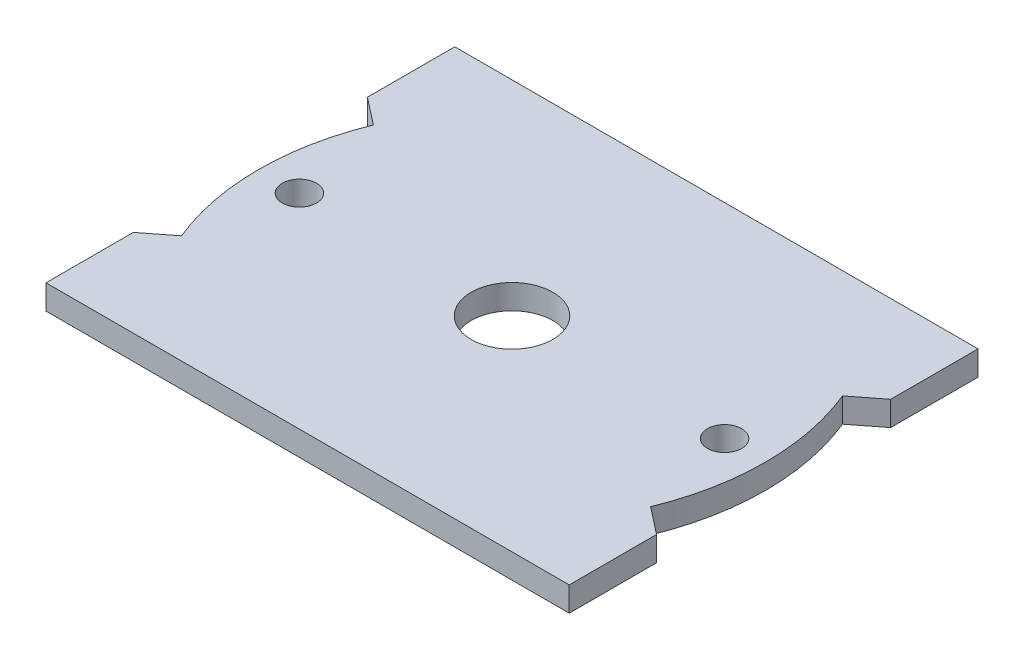
SolidWorks part; units mm, degrees
ref_plane "Front Plane" through (0, 0, 0) normal (0, 0, 1) x (1, 0, 0)
ref_plane "Top Plane" through (0, 0, 0) normal (0, 1, 0) x (1, 0, 0)
ref_plane "Right Plane" through (0, 0, 0) normal (1, 0, 0) x (0, 0, -1)
sketch "Sketch1" plane through (0, 0, 0) normal (0, 1, 0) x (1, 0, 0)
  line L0 (-32, 25) -> (32, -25) construction
  line L1 (32, -25) -> (-32, -25)
  line L2 (32, -25) -> (32, 25)
  line L3 (32, 25) -> (-32, 25)
  line L4 (-32, -25) -> (-32, 25)
  line L5 (0, 25) -> (0, -25) construction
  line L6 (32, 0) -> (-32, 0) construction
  line L7 (-32, -25) -> (32, 25) construction
  line L8 (-18.3303, 25) -> (-11.2626, 19.4783)
  line L9 (-28.6924, 11.7365) -> (-21.6247, 6.2148)
  line L10 (-32, -25) -> (-17.7305, -13.852)
  line L11 (18.3303, 25) -> (11.2626, 19.4783)
  line L12 (-11.2626, -19.4783) -> (-18.3303, -25)
  line L13 (-28.6924, 11.7365) -> (-32, 14.3205)
  line L14 (-21.6247, -6.2148) -> (-32, -14.3205)
  line L15 (28.6924, 11.7365) -> (21.6247, 6.2148)
  line L16 (21.6247, -6.2148) -> (32, -14.3205)
  line L17 (11.2626, -19.4783) -> (18.3303, -25)
  line L18 (28.6924, 11.7365) -> (32, 14.3205)
  line L19 (15.2315, 27) -> (15.2315, 25)
  line L20 (34, -27) -> (-34, -27)
  line L21 (34, -27) -> (34, 27)
  line L22 (34, 27) -> (-34, 27)
  line L23 (-34, -27) -> (-34, 27)
  line L24 (0, 27) -> (0, -27) construction
  line L25 (34, 0) -> (-34, 0) construction
  line L26 (15.2315, 25) -> (32, 25)
  line L27 (32, 14.3205) -> (34, 14.3205)
  line L28 (34, 14.3205) -> (34, 27)
  line L29 (-32, 14.3205) -> (-34, 14.3205)
  line L30 (-15.2315, 27) -> (-15.2315, 25)
  line L31 (32, -14.3205) -> (34, -14.3205)
  line L32 (15.2315, -27) -> (15.2315, -25)
  line L33 (-15.2315, -27) -> (-15.2315, -25)
  line L34 (-32, -14.3205) -> (-34, -14.3205)
  circle A0 centre (0, 0) radius 22.5
  arc A1 (-18.3303, 25) -> (-18.3303, -25) centre (0, 0) ccw
  circle A2 centre (-26, 0) radius 2.1
  circle A3 centre (26, 0) radius 2.1
  arc A4 (18.3303, -25) -> (18.3303, 25) centre (0, 0) ccw
  circle A5 centre (0, 0) radius 5
  point P33 (15.2315, 27)
  dimension "D1" = 45
  dimension "D2" = 62
  dimension "D5" = 4.2
  dimension "D9" = 10
  dimension "D3" = 64
  dimension "D4" = 50
  dimension "D6" = 26
  dimension "D7" = 68
  dimension "D8" = 54
extrude "Boss-Extrude2" add sketch "Sketch1" along normal blind 3 contours A1 L3 L4 L13 | L8 A1 L9 A0 | A0 L11 L3 L8 | L15 A4 L11 A0 | A4 L18 L2 L3 | L16 A4 L15 A0 A3 | L14 A1 L10 A0 | L9 A1 L14 A0 A2 | A1 L14 L4 L10 | A1 L10 L1 | L10 A1 L12 A0 | A0 L12 L1 L17 | L17 A4 L16 A0 | A4 L1 L2 L16 | A0 region at (27.5253, 0, 20.1834) region at (0, 0, 23.1509) region at (20.7114, 0, 16.1808) region at (25.3141, 0, 8.7765) region at (27.5253, 0, -20.1834) region at (-18.0979, 0, 19.5261) region at (20.7114, 0, -16.1808) region at (-25.0676, 0, 23.0669) region at (-23.325, 0, 12.8355) region at (0, 0, -23.1509) region at (-29.2139, 0, 18.2023) region at (-25.3141, 0, 8.7765) region at (-20.7114, 0, -16.1808) region at (-27.5253, 0, -20.1834)
extrude "Cut-Extrude2" cut sketch "Sketch1<14>" along normal blind 10 contours A5
sketch "Sketch1<14>" plane through (0, 0, 0) normal (0, 1, 0) x (1, 0, 0) same geometry as "Sketch1"
